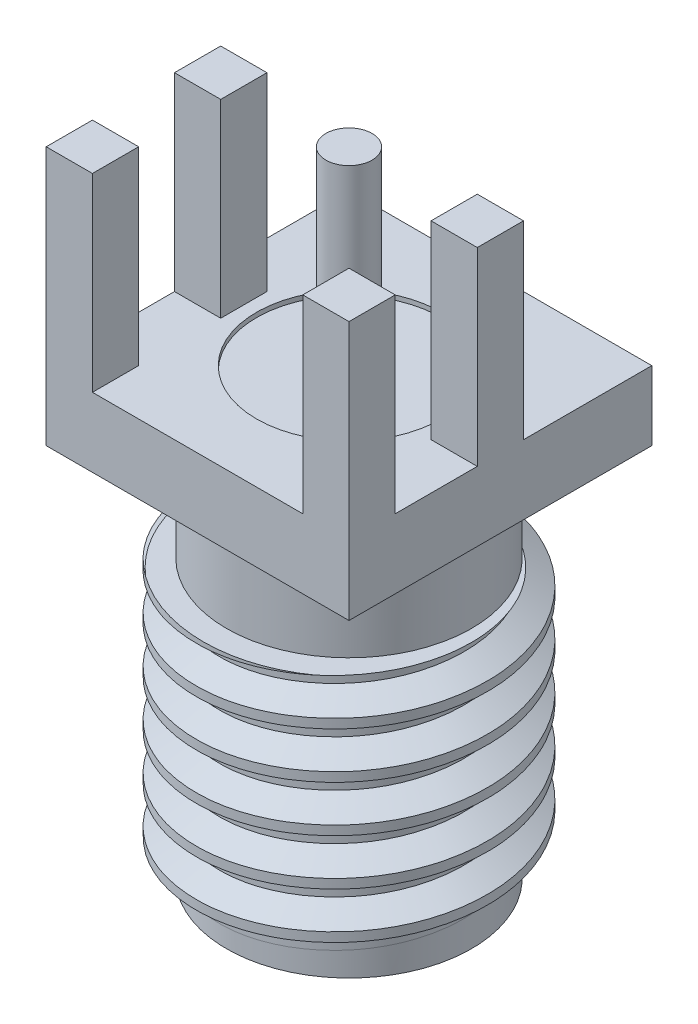
SolidWorks part; units mm, degrees
ref_plane "Front Plane" through (0, 0, 0) normal (0, 0, 1) x (1, 0, 0)
ref_plane "Top Plane" through (0, 0, 0) normal (0, 1, 0) x (1, 0, 0)
ref_plane "Right Plane" through (0, 0, 0) normal (1, 0, 0) x (0, 0, -1)
sketch "Sketch1" plane through (0, 0, 0) normal (0, 1, 0) x (1, 0, 0)
  line L1 (-3.275, 3.275) -> (3.275, 3.275)
  line L2 (-3.275, 3.275) -> (-3.275, -3.275)
  line L3 (-3.275, -3.275) -> (3.275, -3.275)
  line L4 (3.275, 3.275) -> (3.275, -3.275)
  line L5 (-3.275, 3.275) -> (3.275, -3.275) construction
  line L6 (-3.275, -3.275) -> (3.275, 3.275) construction
  point P0 (0, 0)
  dimension "D1" = 6.55
  dimension "D2" = 6.55
extrude "Boss-Extrude1" add sketch "Sketch1" along normal blind 1.5
sketch "Sketch2" plane through (0, 1.5, 0) normal (0, 1, 0) x (1, 0, 0)
  line L0 (-3.275, 0) -> (3.275, 0) construction
  line L1 (-3.275, 3.275) -> (-3.275, -3.275) construction
  line L2 (3.275, -3.275) -> (3.275, 3.275) construction
  line L3 (-3.275, 0) -> (-2.275, 0) construction
  line L4 (-3.275, -3.275) -> (-2.275, -3.275)
  line L5 (-3.275, -3.275) -> (-3.275, -2.275)
  line L6 (-3.275, -2.275) -> (-2.275, -2.275)
  line L7 (-2.275, -3.275) -> (-2.275, -2.275)
  line L8 (-3.275, 0.5) -> (-2.275, 0.5)
  line L9 (-3.275, 0.5) -> (-3.275, -0.5)
  line L10 (-3.275, -0.5) -> (-2.275, -0.5)
  line L11 (-2.275, 0.5) -> (-2.275, -0.5)
  line L12 (0, 3.275) -> (0, -3.275) construction
  line L13 (3.275, 3.275) -> (-3.275, 3.275) construction
  line L14 (-3.275, -3.275) -> (3.275, -3.275) construction
  line L15 (-3.275, 0.5) -> (-2.275, 0.5)
  line L16 (-3.275, -0.5) -> (-2.275, -0.5)
  line L17 (-3.275, 0.5) -> (-3.275, -0.5)
  line L18 (2.275, -3.275) -> (2.275, -2.275)
  line L19 (3.275, -3.275) -> (2.275, -3.275)
  line L20 (3.275, -3.275) -> (3.275, -2.275)
  line L21 (3.275, -2.275) -> (2.275, -2.275)
  line L22 (3.275, -0.5) -> (2.275, -0.5)
  line L23 (2.275, 0.5) -> (2.275, -0.5)
  line L24 (3.275, 0.5) -> (2.275, 0.5)
  line L25 (3.275, 0.5) -> (3.275, -0.5)
  circle A0 centre (0, 0) radius 0.5
  line M1 (3.275, -3.275) -> (3.275, 3.275)
  line M3 (-3.275, 3.275) -> (-3.275, -3.275)
  line M4 (-3.275, -3.275) -> (3.275, -3.275)
  dimension "D3" = 1
  dimension "D1" = 1
  dimension "D2" = 1
extrude "Boss-Extrude2" add sketch "Sketch2" along normal blind 4.1 contours L11 L8 L10 M3 | L7 L6 M4 M3 | L21 L18 M1 M4 | L24 L23 L22 M1 | A0 region at (-2.775, 1.5, 2.775) region at (-2.775, 1.5, 0) region at (2.775, 1.5, 0) region at (2.775, 1.5, 2.775) region at (0, 1.5, 0)
sketch "Sketch3" plane through (0, 1.5, 0) normal (0, 1, 0) x (1, 0, 0)
  circle A0 centre (0, 0) radius 0.5 construction
  circle A1 centre (0, 0) radius 0.5
  circle A2 centre (0, 0) radius 2
  dimension "D1" = 4
extrude "Cut-Extrude1" cut sketch "Sketch3" against normal blind 0.1
sketch "Sketch4" plane through (0, 0, 0) normal (0, -1, 0) x (1, 0, 0)
  circle A0 centre (0, 0) radius 2.65
  dimension "D1" = 5.3
extrude "Boss-Extrude3" add sketch "Sketch4" along normal blind 8.1
sketch "Sketch5" plane through (0, -8.1, 0) normal (0, -1, 0) x (1, 0, 0)
  circle A0 centre (0, 0) radius 2.415
  dimension "D1" = 4.83
extrude "Cut-Extrude2" cut sketch "Sketch5" against normal blind 2.25
sketch "Sketch6" plane through (0, -5.85, 0) normal (0, -1, 0) x (1, 0, 0)
  circle A0 centre (0, 0) radius 0.25
  dimension "D1" = 0.5
extrude "Cut-Extrude3" cut sketch "Sketch6" against normal blind 2
sketch "Sketch7" plane through (0, -8.1, 0) normal (0, -1, 0) x (1, 0, 0)
  circle A1 centre (0, 0) radius 2.65
  circle A2 centre (0, 0) radius 2.65 construction
  circle A3 centre (0, 0) radius 3.15
  dimension "D1" = 0.5
extrude "Boss-Extrude4" add sketch "Sketch7" against normal blind 6
sketch "Sketch12" plane through (0, 0, 0) normal (1, 0, 0) x (0, 0, -1)
  line L0 (2.65, -8.1) -> (3.15, -8.1) construction
  line L1 (3.15, -8.1) -> (3.15, -2.1) construction
  line L2 (3.15, -8.5) -> (2.65, -8.2)
  line L3 (2.65, -8.2) -> (2.65, -8)
  line L4 (2.65, -8) -> (3.15, -7.7)
  line L5 (-3.15, -8.1) -> (3.15, -8.1) construction
  line L6 (3.15, -7.7) -> (3.15, -8.5)
  dimension "D1" = 0.8
  dimension "D3" = 0.5
  dimension "D4" = 0.2
sketch "Sketch13" plane through (0, -8.1, 0) normal (0, -1, 0) x (1, 0, 0)
  circle A0 centre (0, 0) radius 3.15
  circle A1 centre (0, 0) radius 3.15 construction
curve "Helix/Spiral2" pitch 1 height 7 radius 3.15 centre (0, -8.1, 0) axis (0, 1, 0) start towards (1, 0, 0)
sweep "Cut-Sweep3" cut profiles "Sketch12" path "Helix/Spiral2"
sketch "Sketch14" plane through (0, -8.1, 0) normal (0, -1, 0) x (1, 0, 0)
  circle A0 centre (0, 0) radius 3.15
  circle A1 centre (0, 0) radius 3.15 construction
  circle A2 centre (0, 0) radius 2.65
  dimension "D1" = 0.5
extrude "Cut-Extrude4" cut sketch "Sketch14" against normal blind 0.8
